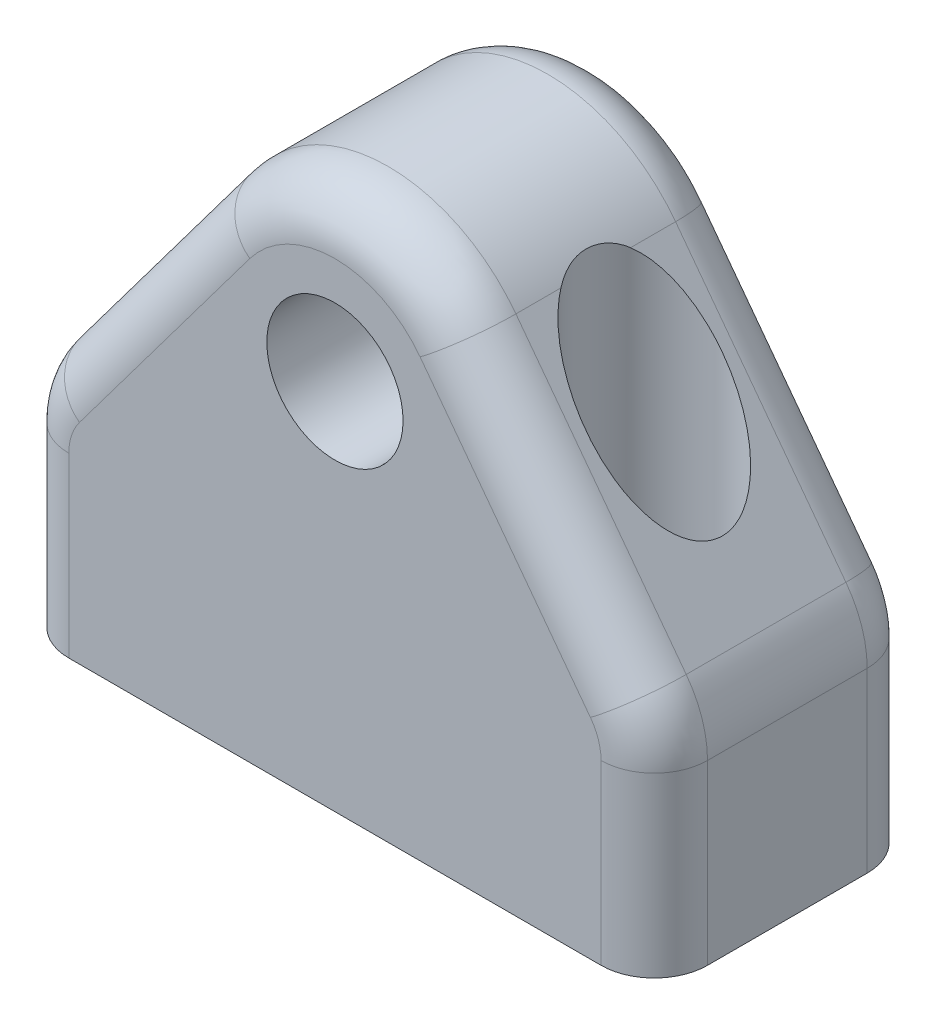
SolidWorks part; units mm, degrees
ref_plane "Front Plane" through (0, 0, 0) normal (0, 0, 1) x (1, 0, 0)
ref_plane "Top Plane" through (0, 0, 0) normal (0, 1, 0) x (1, 0, 0)
ref_plane "Right Plane" through (0, 0, 0) normal (1, 0, 0) x (0, 0, -1)
sketch "Sketch1" plane through (0, 0, 0) normal (0, 0, 1) x (1, 0, 0)
  line L0 (0, 0) -> (0, 5.2917)
  line L1 (0.635, 7.1967) -> (5.715, 13.97)
  line L2 (13.335, 13.97) -> (18.415, 7.1967)
  line L3 (19.05, 5.2917) -> (19.05, 0)
  line L4 (19.05, 0) -> (0, 0)
  arc A0 (5.715, 13.97) -> (13.335, 13.97) centre (9.525, 11.1125) cw
  arc A1 (18.415, 7.1967) -> (19.05, 5.2917) centre (15.875, 5.2917) cw
  arc A2 (0, 5.2917) -> (0.635, 7.1967) centre (3.175, 5.2917) cw
  circle A3 centre (9.525, 11.1125) radius 2.032
  point P13 (0, 6.35)
  dimension "D1" = 4.7625
  dimension "D5" = 3.175
  dimension "D6" = 4.064
  dimension "D2" = 19.05
  dimension "D3" = 6.35
  dimension "D4" = 11.1125
extrude "Boss-Extrude1" add sketch "Sketch1" along normal blind 7.9375
sketch "Sketch2" plane through (0, 0, 0) normal (0, -1, 0) x (1, 0, 0)
  line L0 (0, 7.9375) -> (0, 0) construction
  line L1 (0, 3.9688) -> (3.9688, 3.9688) construction
  line L2 (3.9688, 3.9688) -> (15.0812, 3.9688) construction
  line L3 (15.0812, 3.9688) -> (19.05, 3.9688) construction
  line L4 (19.05, 7.9375) -> (19.05, 0) construction
  circle A0 centre (3.9688, 3.9688) radius 2.032
  circle A1 centre (15.0812, 3.9688) radius 2.032
  point P7 (0, 3.9688)
  dimension "D1" = 4.064
  dimension "D2" = 11.1125
extrude "Cut-Extrude1" cut sketch "Sketch2" against normal through all
fillet "Fillet1" radius 1.5875 14 edges at (19.05, 2.6458, 0) (18.8871, 6.2957, 0) (15.875, 10.5833, 0) (0, 2.6458, 0) (0.1629, 6.2957, 0) (3.175, 10.5833, 0) (19.05, 2.6458, 7.9375) (18.8871, 6.2957, 7.9375) (15.875, 10.5833, 7.9375) (0, 2.6458, 7.9375) (0.1629, 6.2957, 7.9375) (3.175, 10.5833, 7.9375) (9.525, 15.875, 0) (9.525, 15.875, 7.9375)
